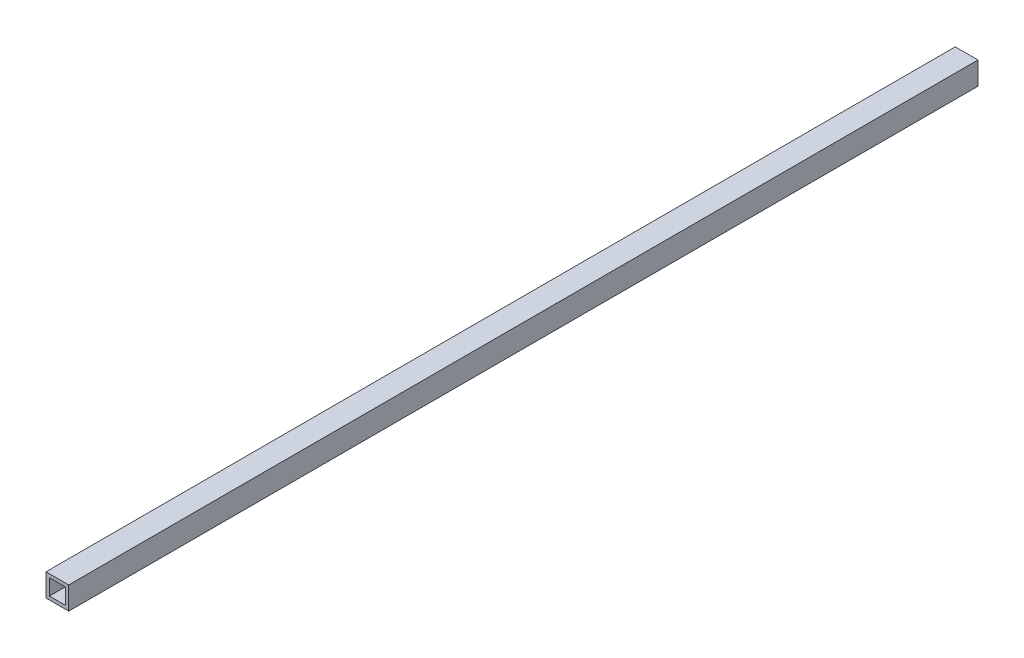
SolidWorks part; units mm, degrees
ref_plane "前视基准面" through (0, 0, 0) normal (0, 0, 1) x (1, 0, 0)
ref_plane "上视基准面" through (0, 0, 0) normal (0, 1, 0) x (1, 0, 0)
ref_plane "右视基准面" through (0, 0, 0) normal (1, 0, 0) x (0, 0, -1)
other "Configuration Table"
sketch "草图1" plane through (0, 0, 0) normal (0, 0, 1) x (1, 0, 0)
  line L0 (-9.3333, 11.0061) -> (-9.3333, -8.9939)
  line L1 (-9.3333, 11.0061) -> (10.6667, 11.0061)
  line L2 (-9.3333, -8.9939) -> (10.6667, -8.9939)
  line L3 (10.6667, 11.0061) -> (10.6667, -8.9939)
  dimension "D1" = 20
  dimension "D2" = 20
extrude "凸台-拉伸1" add sketch "草图1" along normal blind 800
sketch "草图2" plane through (0, 0, 0) normal (0, 0, -1) x (-1, 0, 0)
  line L0 (-10.6667, -8.9939) -> (-10.6667, 11.0061) construction
  line L1 (-7.6667, 8.0061) -> (6.3333, 8.0061)
  line L2 (-7.6667, 8.0061) -> (-7.6667, -5.9939)
  line L3 (-7.6667, -5.9939) -> (6.3333, -5.9939)
  line L4 (6.3333, 8.0061) -> (6.3333, -5.9939)
  line L5 (9.3333, 11.0061) -> (9.3333, -8.9939) construction
  line L6 (9.3333, -8.9939) -> (-10.6667, -8.9939) construction
  line L7 (-10.6667, 11.0061) -> (9.3333, 11.0061) construction
  point P6 (2.1951, -4.305)
  dimension "D1" = 3
  dimension "D2" = 3
  dimension "D3" = 3
  dimension "D4" = 3
extrude "切除-拉伸1" cut sketch "草图2" against normal through all
